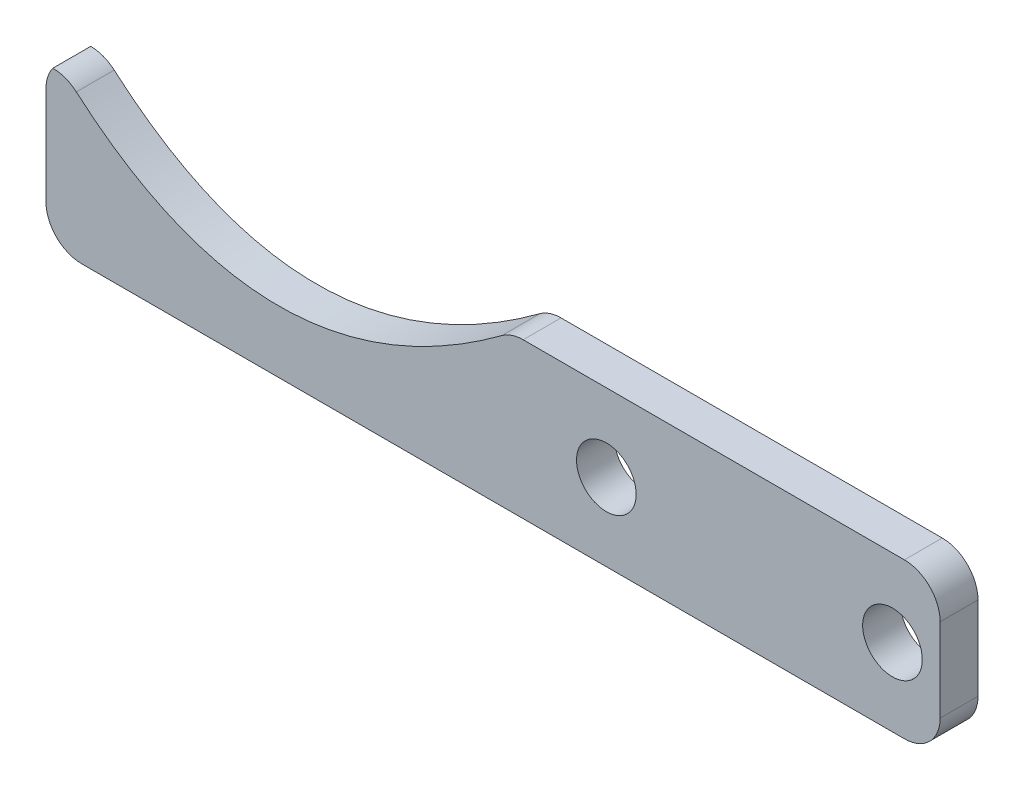
SolidWorks part; units mm, degrees
ref_plane "Front" through (0, 0, 0) normal (0, 0, 1) x (1, 0, 0)
ref_plane "Top" through (0, 0, 0) normal (0, 1, 0) x (1, 0, 0)
ref_plane "Right" through (0, 0, 0) normal (1, 0, 0) x (0, 0, -1)
sketch "Sketch1" plane through (0, 0, 0) normal (0, 0, 1) x (1, 0, 0)
  line L0 (-37.5, 0) -> (37.5, 0) construction
  line L1 (-37.5, -6.5) -> (37.5, -6.5)
  line L2 (-37.5, -6.5) -> (-37.5, 6.5)
  line L3 (-37.5, 6.5) -> (37.5, 6.5)
  line L4 (37.5, -6.5) -> (37.5, 6.5)
  line L5 (-37.5, -6.5) -> (37.5, 6.5) construction
  line L6 (-37.5, 6.5) -> (37.5, -6.5) construction
  circle A0 centre (33.5, 0) radius 2.5
  circle A1 centre (9.5, 0) radius 2.5
  point P0 (0, 0)
  dimension "D3" = 5
  dimension "D5" = 4
  dimension "D1" = 75
  dimension "D2" = 13
  dimension "D4" = 24
extrude "Boss-Extrude1" add sketch "Sketch1" along normal blind 3.175
sketch "Sketch3" plane through (0, 0, 3.175) normal (0, 0, 1) x (1, 0, 0)
  line L0 (37.5, 6.5) -> (-37.5, 6.5) construction
  line L1 (-35.7804, 6.5) -> (1.5202, 6.5)
  spline S0 degree 2 poles (-35.7804, 6.5) (-18.8245, -9.0981) (1.5202, 6.5) knots 0 0 0 1 1 1
extrude "Cut-Extrude1" cut sketch "Sketch3" against normal up to surface (3.175 mm away) up to face at (36, 0, 0)
fillet "Fillet2" radius 3 2 edges at (-35.7804, 6.5, 1.5875) (1.5202, 6.5, 1.5875)
fillet "Fillet3" radius 3 4 edges at (-37.5, -6.5, 1.5875) (-37.5, 6.5, 1.5875) (37.5, -6.5, 1.5875) (37.5, 6.5, 1.5875)
